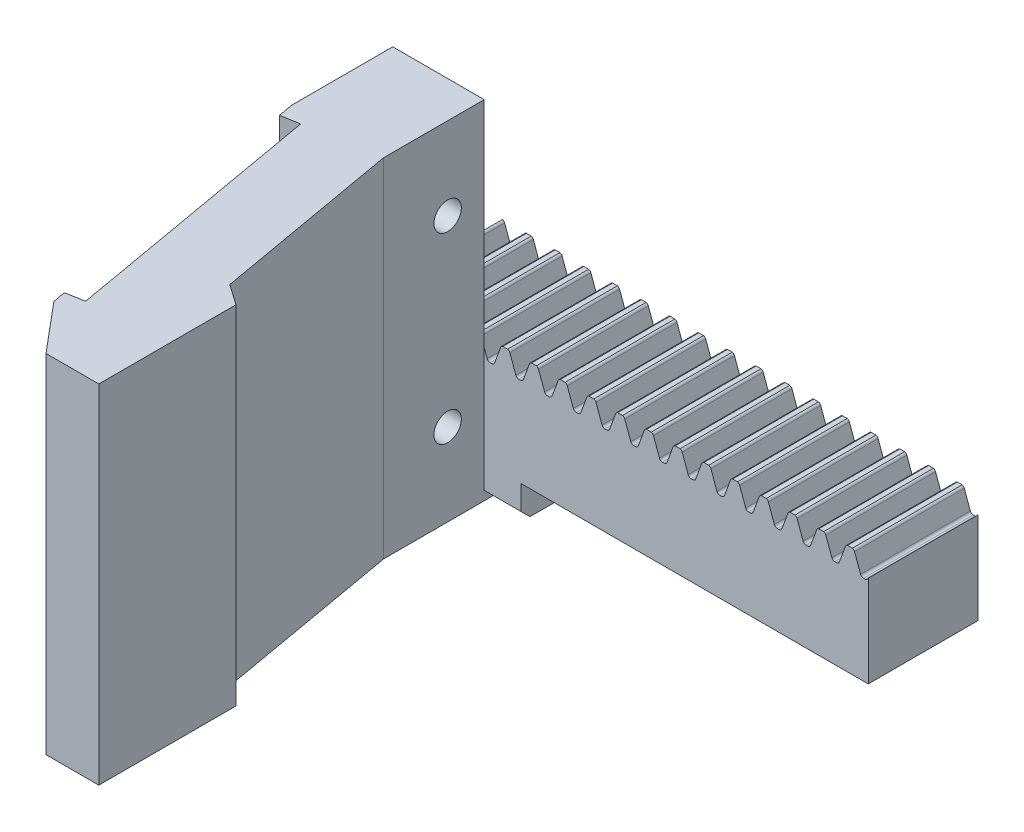
SolidWorks part; units mm, degrees
other "Markup1"
sketch "Sketch7" plane through (-50, -9.66, 16) normal (-0.9886, -0.1404, 0.0537) x (0.0542, 0, 0.9985)
ref_plane "Front Plane" through (0, 0, 0) normal (0, 0, 1) x (1, 0, 0)
ref_plane "Top Plane" through (0, 0, 0) normal (0, 1, 0) x (1, 0, 0)
ref_plane "Right Plane" through (0, 0, 0) normal (1, 0, 0) x (0, 0, -1)
sketch "Sketch1" plane through (0, 0, 0) normal (0, 0, 1) x (1, 0, 0)
  line L0 (-50, 6) -> (-50, -6) construction
  line L1 (-50, -6) -> (50, -6) construction
  line L2 (50, -6) -> (50, 6) construction
  line L4 (0, 6) -> (0, -6) construction
  line L5 (-50, 5) -> (50, 5) construction
  line L6 (-47.5453, 6) -> (-46.7025, 6) construction
  line L7 (-46.7025, 6) -> (-45.8835, 3.75) construction
  line L8 (-47.5453, 6) -> (-48.3643, 3.75) construction
  line L9 (-48.3643, 3.75) -> (-45.8835, 3.75) construction
  line L10 (-47.1239, 6) -> (-47.1239, 3.75) construction
  line L11 (-50, 0) -> (-40.8407, 0) construction
  line L12 (50, 0) -> (40.8407, 0) construction
  point P15 (-43.9823, 6)
  point P16 (-15.5, -6)
  point P17 (-46.3385, 5)
  point P18 (-47.9093, 5)
  point P21 (-0.5, -6)
  dimension "Length" = 100
  dimension "Height" = 12
  dimension "Approximate Number of Teeth" = 31
  dimension "Pressure Angle" = 20
  dimension "Circular Pitch" = 3.1416
  dimension "Addendum" = 1
  dimension "Dedendum" = 1.25
  dimension "Circular Tooth Thickness" = 1.5708
  dimension "Module" = 1
  dimension "Rack Length" = 94.2478
  dimension "D1" = 6.2832
sketch "Sketch2" plane through (0, 0, 0) normal (1, 0, 0) x (0, 0, -1)
  line L0 (-6, 0) -> (6, 0) construction
  dimension "Face Width" = 12
sketch "Sketch3" plane through (0, 0, 0) normal (0, 0, 1) x (1, 0, 0)
  line L1 (-50, 6) -> (50, 6)
  line L2 (-50, 6) -> (-50, -6)
  line L3 (-50, -6) -> (50, -6)
  line L4 (50, 6) -> (50, -6)
extrude "Boss-Extrude1" add sketch "Sketch3" against normal up to vertex (6 mm away) and the other way up to vertex (6 mm away) up to point (0, 0, -6) other way up to point (0, 0, 6)
sketch "Sketch4" plane through (0, 0, 0) normal (0, 0, 1) x (1, 0, 0)
  line L0 (-47.1239, 6) -> (-43.9823, 6) construction
  line L9 (-45.5531, 6) -> (-45.5531, 3.75)
  line L10 (-45.5531, 3.75) -> (-45.8835, 3.75)
  line L11 (-45.8835, 3.75) -> (-46.7025, 6)
  line L12 (-46.7025, 6) -> (-45.5531, 6)
  line L13 (-47.5453, 6) -> (-48.3643, 3.75)
  line L14 (-48.3643, 3.75) -> (-48.6947, 3.75)
  line L15 (-48.6947, 3.75) -> (-48.6947, 6)
  line L16 (-48.6947, 6) -> (-47.5453, 6)
  line L17 (50, 6) -> (-50, 6) construction
  line L18 (-47.5453, 6) -> (-47.3104, 6)
  line L19 (-46.9374, 6) -> (-46.7025, 6)
  arc A0 (-48.5992, 3.75) -> (-48.2839, 3.9708) centre (-48.5992, 4.0855) ccw
  arc A1 (-45.9639, 3.9708) -> (-45.6486, 3.75) centre (-45.6486, 4.0855) ccw
  arc A2 (-47.6257, 5.7792) -> (-47.3104, 6) centre (-47.3104, 5.6645) cw
  arc A3 (-46.9374, 6) -> (-46.6221, 5.7792) centre (-46.9374, 5.6645) cw
  dimension "D1" = 0.3355
extrude "Cut-Extrude1" cut sketch "Sketch4" against normal through all both and the other way through all contours L14 A0 L13 L16 L15 | L13 A2 L18 | L19 A3 L11 | L11 A1 L10 L9 L12 region at (-45.9615, 5.0903, 0) region at (-46.7355, 5.9529, 0) region at (-47.5123, 5.9529, 0) region at (-48.2863, 5.0903, 0)
pattern_linear "LPattern1" count 32 spacing 3.1416 along (1, 0, 0) count 2 spacing 3.1416 along (-1, 0, 0) of "Cut-Extrude1"
sketch "Drawing Refernce 1" plane through (0, 0, 6) normal (0, 0, 1) x (1, 0, 0)
  line L0 (-50, 0) -> (50, 0) construction
  point P6 (-35, 0)
  point P7 (-27.5, 0)
  point P8 (35, 0)
  dimension "D1" = 15
  dimension "D2" = 22.5
  dimension "D3" = 15
sketch "Sketch5" plane through (0, 0, 6) normal (0, 0, 1) x (1, 0, 0)
  line L0 (2, -6) -> (2, 23.2722) construction
  line L1 (-50, -6) -> (50, -6) construction
  line L2 (-50, 5.9906) -> (-50, -6) construction
  line L8 (2, -6) -> (50.3789, -6)
  line L9 (2, -6) -> (2, 6.3802)
  line L10 (2, 6.3802) -> (50.3789, 6.3802)
  line L11 (50.3789, -6) -> (50.3789, 6.3802)
  dimension "D1" = 52
extrude "Cut-Extrude2" cut sketch "Sketch5" against normal through all
sketch "Sketch6" plane through (0, 0, 6) normal (0, 0, 1) x (1, 0, 0)
  line L0 (-50, -6) -> (2, -6) construction
  line L1 (-50, -9.66) -> (-40, -9.66)
  line L2 (-50, -9.66) -> (-50, 50.34)
  line L3 (-50, 50.34) -> (-40, 50.34)
  line L4 (-40, -9.66) -> (-40, 50.34)
  line L5 (-50, 5.9906) -> (-50, -6) construction
  dimension "D1" = 10
  dimension "D2" = 3.66
  dimension "D3" = 60
extrude "Boss-Extrude2" add sketch "Sketch6" along normal blind 8
sketch "Sketch8" plane through (-50, 0, 0) normal (-1, 0, 0) x (0, 0, 1)
  line L1 (14, 50.34) -> (14, -9.66) construction
  circle A0 centre (10, 19.34) radius 1.5
  circle A1 centre (10, -0.66) radius 1.5
  dimension "D1" = 3
  dimension "D2" = 3
  dimension "D3" = 4
  dimension "D4" = 4
  dimension "D5" = 20
extrude "Cut-Extrude3" cut sketch "Sketch8" against normal through all
sketch "Sketch9" plane through (0, 0, 14) normal (0, 0, 1) x (1, 0, 0)
  line L0 (-40, -9.66) -> (-40, 50.34) construction
  line L1 (-50, 50.34) -> (-38.86, 50.34)
  line L2 (-50, 50.34) -> (-50, -9.66)
  line L3 (-50, -9.66) -> (-38.86, -9.66)
  line L4 (-38.86, 50.34) -> (-38.86, -9.66)
  dimension "D1" = 1.14
extrude "Boss-Extrude3" add sketch "Sketch9" along normal blind 40
sketch "Sketch10" plane through (0, -9.66, 0) normal (0, -1, 0) x (1, 0, 0)
  line L0 (-50, 44) -> (-38.86, 44) construction
  line L1 (-50, 54) -> (-50, 6) construction
  line L2 (-38.86, 54) -> (-38.86, 14) construction
  line L3 (-50, 54) -> (-38.86, 54) construction
  line L5 (-38.86, 44) -> (-38.86, 14)
  line L6 (-38.86, 14) -> (-40, 14)
  line L7 (-40, 14) -> (-40, 44)
  line L8 (-40, 44) -> (-38.86, 44)
  dimension "D1" = 10
extrude "Cut-Extrude4" cut sketch "Sketch10" against normal through all both
chamfer "Chamfer1" distance 12 angle 45 1 edges at (-45, -6, 6)
sketch "Sketch11" plane through (-50, 0, 0) normal (-1, 0, 0) x (0, 0, 1)
  line L5 (-2.34, -9.66) -> (-6, -6)
  line L6 (-6, -6) -> (-6, 5.9906)
  line L7 (-6, 5.9906) -> (6, 5.9906)
  line L8 (6, 5.9906) -> (6, 50.34)
  line L9 (48.3431, 50.34) -> (54, 44.6831)
  line L10 (54, -4.0031) -> (48.3431, -9.66)
  line L11 (43.5443, -10.137) -> (43.4726, -9.66)
  line L12 (-2.34, -9.66) -> (48.3431, -9.66)
  line L13 (6, 50.34) -> (48.3431, 50.34)
  line L14 (54, 44.6831) -> (54, -4.0031)
  circle M13 centre (10, 19.34) radius 1.5
  circle M14 centre (10, -0.66) radius 1.5
  line M15 (6, 5.9906) -> (-6, 5.9906)
  line M16 (-6, 5.9906) -> (-6, -6)
  line M17 (-6, -6) -> (-2.34, -9.66)
  line M18 (-2.34, -9.66) -> (54, -9.66)
  line M19 (54, -9.66) -> (54, 50.34)
  line M20 (54, 50.34) -> (6, 50.34)
  line M21 (6, 50.34) -> (6, 5.9906)
  dimension "D3" = 8
extrude "Cut-Extrude7" cut sketch "Sketch11" against normal blind 71 flip side to cut contours L10 L9 M19 M20 M21 M15 M16 M17 M18 M14 M13 region at (-50, 19.0742, 28.0676)
sketch "Sketch12" plane through (-40, 0, 0) normal (1, 0, 0) x (0, 0, -1)
  line L0 (-54, 44.6831) -> (-54, -9.66)
  line L1 (-44, 50.34) -> (-6, 50.34) construction
  line L2 (-17, 50.34) -> (-17, -9.66)
  line L3 (-44, -9.66) -> (2.34, -9.66) construction
  line L4 (-54, 50.34) -> (-17, 50.34)
  line L5 (-54, 44.6831) -> (-54, 50.34)
  line L7 (-54, -9.66) -> (-17, -9.66)
extrude "Cut-Extrude8" cut sketch "Sketch12" against normal blind 30 and the other way blind 30
sketch "Sketch13" plane through (0, -9.66, 0) normal (0, -1, 0) x (1, 0, 0)
  line L1 (-40, 17) -> (-36.3987, 37.4238)
  line L5 (-50, 17) -> (-40, 17)
  line L6 (-50, 17) -> (-44.4214, 48.6377)
  line L7 (-50, 17) -> (-50, 54)
  line L8 (-44.4214, 48.6377) -> (-39.9219, 54)
  line L10 (-34.1477, 39) -> (-34.1477, 54)
  line L11 (-34.1477, 54) -> (-39.9219, 54)
  line L12 (-36.3987, 37.4238) -> (-34.1477, 39)
  line M13 (-40, 17) -> (-50, 17)
  dimension "D1" = 80
  dimension "D2" = 80
  dimension "D3" = 150
  dimension "D4" = 7
  dimension "D5" = 37
  dimension "D6" = 15
  dimension "D7" = 135
extrude "Boss-Extrude4" add sketch "Sketch13" against normal blind 60 contours L1 L12 L10 L11 L8 L6 M13 region at (-41.5109, -9.66, 35.2395)
sketch "Sketch14" plane through (-51.3995, 0, 9.0631) normal (-0.9848, 0, 0.1736) x (0.1736, 0, 0.9848)
  line L0 (8.0593, 50.34) -> (8.0593, -9.66)
  line L1 (8.0593, -9.66) -> (40.1851, -9.66)
  line L2 (40.1851, -9.66) -> (40.1851, 50.34)
  line L3 (40.1851, 50.34) -> (8.0593, 50.34)
  line L4 (8.0593, 50.34) -> (9.7709, 48.7542)
  line L5 (9.7709, 48.7542) -> (38.7709, 48.7542)
  line L6 (38.7709, 48.7542) -> (40.1851, 50.34)
  line L7 (38.7709, 48.7542) -> (38.7709, -8.2458)
  line L8 (38.7709, -8.2458) -> (40.1851, -9.66)
  line L9 (38.7709, -8.2458) -> (9.7709, -8.2458)
  line L10 (9.7709, -8.2458) -> (8.0593, -9.66)
  line L11 (9.7709, -8.2458) -> (9.7709, 48.7542)
  dimension "D1" = 29
  dimension "D2" = 57
  dimension "D4" = 45
extrude "Cut-Extrude9" cut sketch "Sketch14" against normal blind 2 contours L11 L9 L7 L5 region at (-47.1849, 20.2542, 32.9652)
chamfer "Chamfer2" distance 4 angle 45 4 edges at (-48.718, -8.2458, 18.5119) (-43.6822, -8.2458, 47.0713) (-48.718, 48.7542, 18.5119) (-43.6822, 48.7542, 47.0713)
sketch "Sketch17" plane through (0, -6, 0) normal (0, -1, 0) x (1, 0, 0)
  line L0 (-40, -6) -> (-36, -6)
  line L1 (-36, -6) -> (-36, 6)
  line L2 (-40, 6) -> (2, 6) construction
  line L3 (-36, 6) -> (-40, 6)
  line L4 (-40, 6) -> (-40, -6)
  line L6 (-40, -6) -> (2, -6) construction
extrude "Boss-Extrude5" add sketch "Sketch17" along normal blind 3.66
ref_plane "Plane1" through (2, -6, -6) normal (-1, 0, 0) x (0, 0, 1)
ref_plane "Plane2" through (-40, -6, -6) normal (1, 0, 0) x (0, 0, -1)
sketch "Sketch20" plane through (0, -9.66, 0) normal (0, -1, 0) x (1, 0, 0)
  line L0 (-40, -6) -> (-50, -6)
  line L1 (-50, -6) -> (-50, -2.34)
  line L2 (-50, -2.34) -> (-40, -2.34)
  line L3 (-40, -2.34) -> (-40, -6)
extrude "Boss-Extrude6" add sketch "Sketch20" against normal blind 5.66
chamfer "Chamfer8" distance 1 angle 45 1 edges at (-38, -9.66, 6)
sketch "Sketch21" plane through (0, -9.66, 0) normal (0, -1, 0) x (1, 0, 0)
  circle A0 centre (-43, -0.5) radius 2.5
  dimension "D2" = 5
extrude "Cut-Extrude10" cut sketch "Sketch21" against normal blind 10
sketch "Sketch22" plane through (0, -9.66, 0) normal (0, -1, 0) x (1, 0, 0)
  circle A0 centre (-43, -0.5) radius 3.95
  dimension "D2" = 7.9
extrude "Cut-Extrude11" cut sketch "Sketch22" against normal blind 8
sketch "Sketch25" plane through (-40, 0, 0) normal (1, 0, 0) x (0, 0, -1)
  line L0 (-6, -8.66) -> (-6, -9.66)
  line L1 (-17, -9.66) -> (-5, -9.66) construction
  line L3 (-6, 4.848) -> (-6, 50.34) construction
  line L4 (-6, -9.66) -> (-13.1303, -9.66)
  line L5 (-6, 28.34) -> (-71.1138, 28.34)
  line L6 (-71.1138, 28.34) -> (-71.1138, 51.9644)
  line L7 (-71.1138, 51.9644) -> (-6, 51.9644)
  line L8 (-6, 51.9644) -> (-6, 28.34)
  line M7 (-6, 4.848) -> (-6, 50.34)
  line M8 (-6, 50.34) -> (-17, 50.34)
  line M9 (-17, 50.34) -> (-17, -9.66)
  dimension "D1" = 38
extrude "Cut-Extrude13" cut sketch "Sketch25" against normal blind 10 and the other way blind 10 contours L8 L7 L6 L5 M9 M8 | L5 M7 M8 M9 region at (-40, 39.34, 11.5) region at (-40, 40.3038, 43.6082)
equation "\"Diametral Pitch\"= 1 / \"Module\""
equation "\"Pressure Angle\"=20"
equation "\"Dedendum\"= 1.25 / \"Diametral Pitch\""
equation "\"Addendum\"= 1 / \"Diametral Pitch\""
equation "\"WorkingDepth\"= 2 / \"Diametral Pitch\""
equation "\"WholeDepth\"= 2.25 / \"Diametral Pitch\""
equation "\"Clearance\"= 0.25 / \"Diametral Pitch\""
equation "\"ToothThickness\"= ( pi / 2 ) / \"Diametral Pitch\""
equation "\"CircularPitch\"= pi / \"Diametral Pitch\""
equation "\"Fillet\"= \"Clearance\" * cos ( \"Pressure Angle\" ) * tan ( ( 90 + \"Pressure Angle\" ) / 2 )"
equation "\"Module\"= 1"
equation "\"Addendum@Sketch1\"=\"Addendum\""
equation "\"Pressure Angle@Sketch1\"=\"Pressure Angle\""
equation "\"Dedendum@Sketch1\"=\"Dedendum\""
equation "\"Circular Pitch@Sketch1\"=\"CircularPitch\""
equation "\"Circular Tooth Thickness@Sketch1\"=\"ToothThickness\""
equation "\"Module@Sketch1\"=\"Module\""
equation "\"Approximate Number of Teeth@Sketch1\" = int ( \"Length@Sketch1\" /  ( 2 * \"Circular Tooth Thickness@Sketch1\" )  ) "
equation "\"Rack Length@Sketch1\" = \"Circular Pitch@Sketch1\" *  ( \"Approximate Number of Teeth@Sketch1\" - 1 ) "
equation "\"D3@LPattern1\"=\"CircularPitch\""
equation "\"D1@LPattern1\"=\"Approximate Number of Teeth@Sketch1\"+1"
equation "\"D1@Sketch1\"=\"Circular Pitch@Sketch1\"*2"
equation "\"D1@Sketch4\"=\"Fillet\""
equation "\"D4@LPattern1\"=\"CircularPitch\""
equation "\"D2@Drawing Refernce 1\"=\"D1@Drawing Refernce 1\"*1.5"
equation "\"D3@Drawing Refernce 1\"=\"D1@Drawing Refernce 1\""
